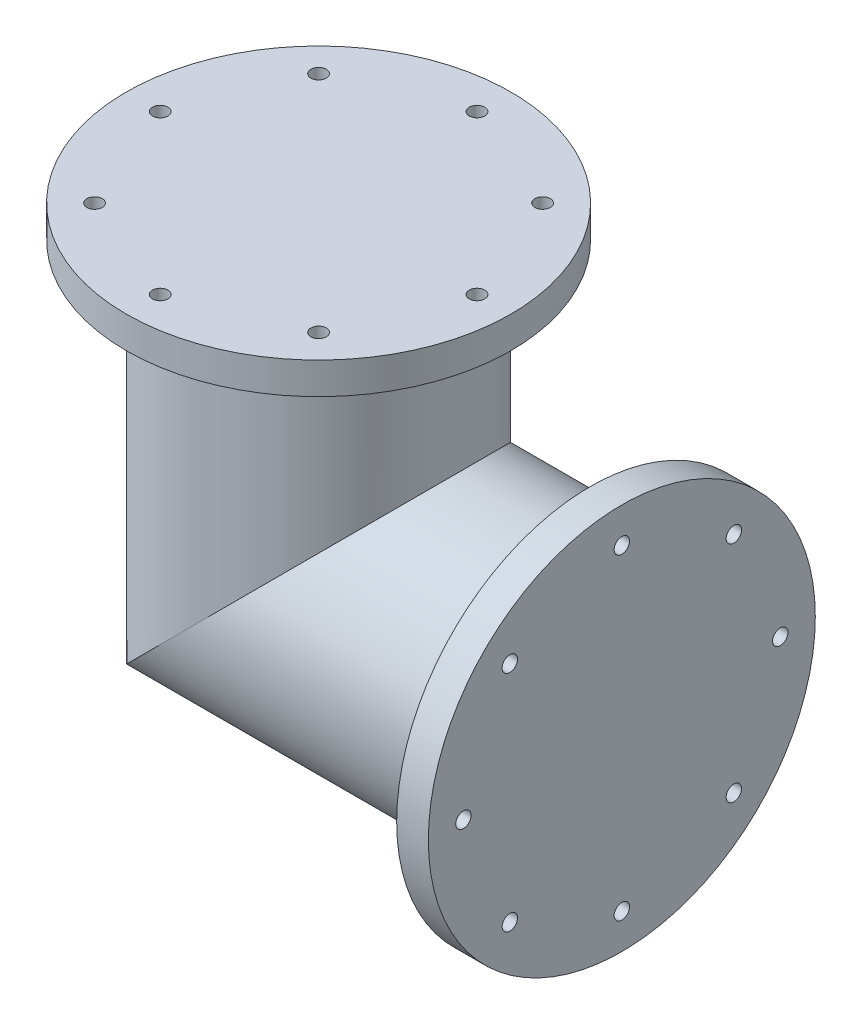
SolidWorks part; units mm, degrees
other "Elemento de detalle1"
other "Carpeta de soldadura"
other "Cordón de soldadura1"
material "7075-O (SS)"
ref_plane "Front" through (0, 0, 0) normal (0, 0, 1) x (1, 0, 0)
ref_plane "Top" through (0, 0, 0) normal (0, 1, 0) x (1, 0, 0)
ref_plane "Right" through (0, 0, 0) normal (1, 0, 0) x (0, 0, -1)
sketch "Croquis1" plane through (0, 0, 0) normal (1, 0, 0) x (0, 0, -1)
  circle A0 centre (0, 0) radius 42.75
  dimension "D1" = 85.5
extrude "Saliente-Extruir1" add sketch "Croquis1" along normal mid plane 7
sketch "Croquis2" plane through (0, 0, 0) normal (0, 0, 1) x (1, 0, 0)
  line L0 (-13.5, -50) -> (-63.5, 0) construction
  line L2 (3.85, 0) -> (-3.85, 0) construction
  line L4 (-3.5, 42.75) -> (-3.5, -42.75) construction
  dimension "D1" = 45
  dimension "D2" = 10
  dimension "D3" = 50
ref_plane "Plano1" through (-63.5, 0, 0) normal (-0.7071, 0.7071, 0) x (0, 0, 1)
sketch "Croquis3" plane through (-3.5, 0, 0) normal (-1, 0, 0) x (0, 0, 1)
  circle A0 centre (0, 0) radius 30
  circle A1 centre (0, 0) radius 25
  dimension "D1" = 60
  dimension "D2" = 50
extrude "Saliente-Extruir2" add sketch "Croquis3" along normal up to surface (60 mm away) up to plane "Plano1"
ref_plane "Plano2" through (0, 60, 0) normal (0, 1, 0) x (1, 0, 0)
sketch "Croquis4" plane through (0, 60, 0) normal (0, 1, 0) x (1, 0, 0)
  circle A0 centre (-63.5, 0) radius 30 construction
  circle A1 centre (-63.5, 0) radius 30
  circle A2 centre (-63.5, 0) radius 25 construction
  circle A3 centre (-63.5, 0) radius 25
extrude "Saliente-Extruir3" add sketch "Croquis4" against normal up to surface (60 mm away) separate body up to face at (-38.5, 25, 0)
hole_wizard "Refrentado para tornillo con cabeza troncocónica de M31" positions "Croquis5" profile "Croquis7" counterbore size "M3" standard "Ansi Metric" end condition up to next
sketch "Croquis5" plane through (-3.5, 0, 0) normal (-1, 0, 0) x (0, 0, 1)
  line L0 (0, -47.025) -> (0, 47.025) construction
  line L1 (47.025, 0) -> (-47.025, 0) construction
  point P0 (0, 35)
  point P12 (24.7487, 24.7487)
  point P13 (35, 0)
  point P14 (24.7487, -24.7487)
  point P15 (0, -35)
  point P16 (-24.7487, -24.7487)
  point P17 (-35, 0)
  point P18 (-24.7487, 24.7487)
  dimension "D1" = 35
  dimension "D2" = 8
sketch "Croquis7" plane through (-3.5, 35, 0) normal (0, 1, 0) x (0, 0, 1)
  line L0 (0, 0) -> (0, 7)
  line L1 (0, 7) -> (1.7, 7)
  line L3 (1.7, 7) -> (1.7, 2.4)
  line L4 (1.7, 2.4) -> (3.5, 2.4)
  line L5 (3.5, 2.4) -> (3.5, 0)
  line L7 (3.5, 0) -> (0, 0)
  line L11 (0, -6.35) -> (0, 107.95) construction
  dimension "Diámetro de taladro hasta el siguiente" = 3.4
  dimension "Profundidad de taladro hasta el siguiente" = 7
  dimension "Diámetro de refrentado" = 7
  dimension "Profundidad de refrentado" = 2.4
sketch "Croquis8" plane through (0, 60, 0) normal (0, 1, 0) x (1, 0, 0)
  line L0 (-60.3625, 0) -> (60.3625, 0) construction
  circle A0 centre (-63.5, 0) radius 42.5
  circle A1 centre (-63.5, 0) radius 25 construction
  dimension "D1" = 85
extrude "Saliente-Extruir4" add sketch "Croquis8" along normal blind 7
hole_wizard "Refrentado para tornillo con cabeza troncocónica de M32" positions "Croquis9" profile "Croquis10" counterbore size "M3" standard "Ansi Metric" end condition up to next
sketch "Croquis9" plane through (0, 60, 0) normal (0, -1, 0) x (-1, 0, 0)
  line L0 (63.5, 0) -> (63.5, -35) construction
  line L1 (-60.225, 0) -> (60.225, 0) construction
  line L4 (63.5, 0) -> (63.5, 35) construction
  circle A0 centre (63.5, 0) radius 30 construction
  point P0 (63.5, -35)
  point P24 (38.7513, -24.7487)
  point P25 (28.5, 0)
  point P26 (38.7513, 24.7487)
  point P27 (63.5, 35)
  point P28 (88.2487, 24.7487)
  point P29 (98.5, 0)
  point P30 (88.2487, -24.7487)
  dimension "D1" = 35
  dimension "D3" = 8
sketch "Croquis10" plane through (-63.5, 60, 35) normal (1, 0, 0) x (0, 0, -1)
  line L0 (0, 0) -> (0, 7.001)
  line L1 (0, 7.001) -> (1.7, 7.001)
  line L3 (1.7, 7.001) -> (1.7, 2.4)
  line L4 (1.7, 2.4) -> (3.5, 2.4)
  line L5 (3.5, 2.4) -> (3.5, 0)
  line L7 (3.5, 0) -> (0, 0)
  line L11 (0, -6.35) -> (0, 107.95) construction
  dimension "Diámetro de taladro hasta el siguiente" = 3.4
  dimension "Profundidad de taladro hasta el siguiente" = 7.001
  dimension "Diámetro de refrentado" = 7
  dimension "Profundidad de refrentado" = 2.4
